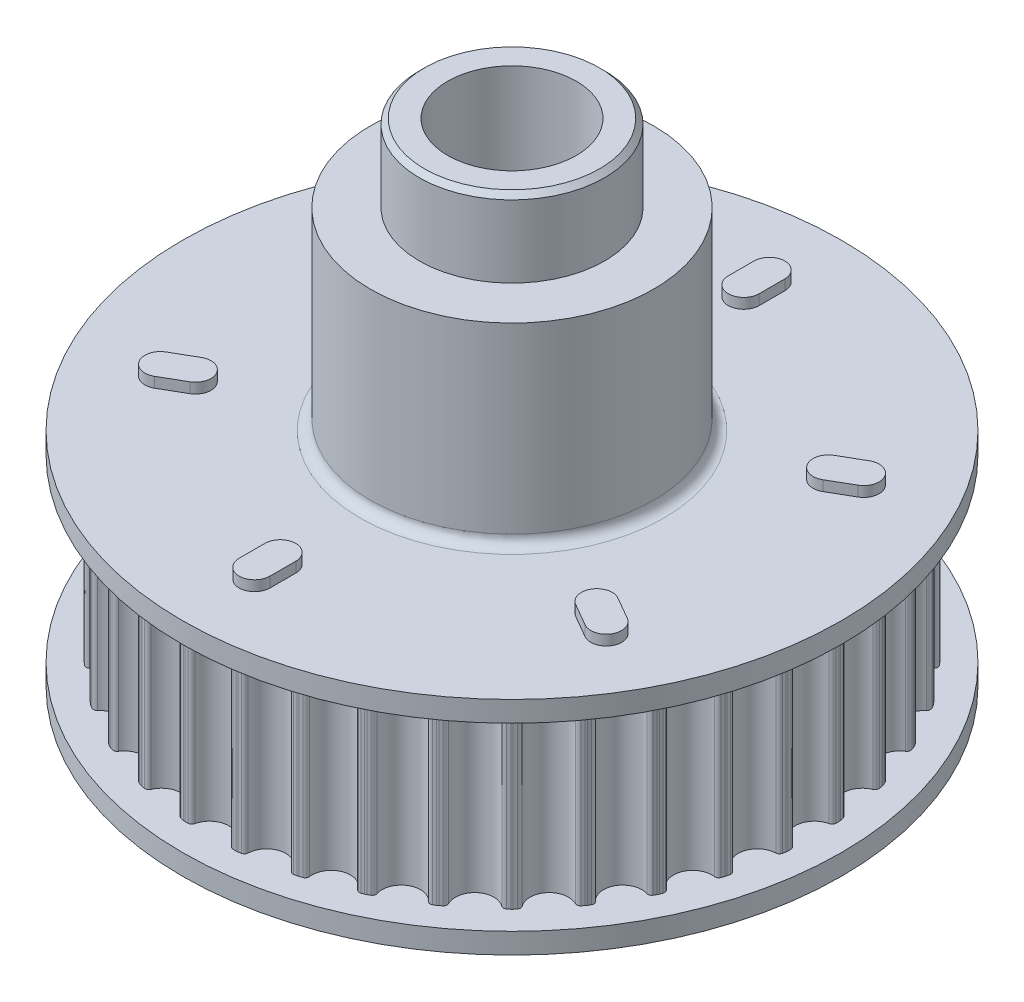
SolidWorks part; units mm, degrees
material "ABS"
ref_plane "Front Plane" through (0, 0, 0) normal (0, 0, 1) x (1, 0, 0)
ref_plane "Top Plane" through (0, 0, 0) normal (0, 1, 0) x (1, 0, 0)
ref_plane "Right Plane" through (0, 0, 0) normal (1, 0, 0) x (0, 0, -1)
sketch "Sketch1" plane through (0, 0, 0) normal (0, 1, 0) x (1, 0, 0)
  circle A0 centre (0, 0) radius 11.75
  circle A1 centre (0, 0) radius 2.5
  dimension "D1" = 23.5
  dimension "D2" = 5
extrude "Boss-Extrude1" add sketch "Sketch1" along normal blind 7
sketch "Sketch2" plane through (0, 7, 0) normal (0, 1, 0) x (1, 0, 0)
  line L0 (0, 0) -> (0, 11.75) construction
  line L1 (-0.8793, 11.708) -> (-1, 11.708)
  line L2 (0.8793, 11.708) -> (1, 11.708)
  line L3 (-1, 11.708) -> (-1, 11.9045)
  line L4 (-1, 11.9045) -> (1, 11.9045)
  line L5 (1, 11.9045) -> (1, 11.708)
  arc A0 (-0.7327, 11.59) -> (0.7327, 11.59) centre (0, 11.75) ccw
  arc A1 (-0.7327, 11.59) -> (-0.8793, 11.708) centre (-0.8793, 11.558) ccw
  arc A2 (0.7327, 11.59) -> (0.8793, 11.708) centre (0.8793, 11.558) cw
  dimension "D1" = 0.75
  dimension "D2" = 0.16
  dimension "D4" = 11.75
  dimension "D6" = 0
  dimension "D7" = 1
  dimension "D5" = 0.15
extrude "Cut-Extrude1" cut sketch "Sketch2" against normal through all
pattern_circular "CirPattern1" count 36 over 360 about axis through (0, 7, 0) along (0, 1, 0) of "Cut-Extrude1"
sketch "Sketch4" plane through (0, 0, 0) normal (0, -1, 0) x (1, 0, 0)
  circle A0 centre (0, 0) radius 3.15
  circle A1 centre (0, 0) radius 12.8
  dimension "D1" = 25.6
extrude "Boss-Extrude4" add sketch "Sketch4" along normal blind 0.8
sketch "Sketch5" plane through (0, 7, 0) normal (0, 1, 0) x (1, 0, 0)
  circle A0 centre (0, 0) radius 2.5
  circle A1 centre (0, 0) radius 12.8
  dimension "D1" = 25.6
  dimension "D2" = 5
extrude "Boss-Extrude5" add sketch "Sketch5" along normal blind 0.8
sketch "Sketch6" plane through (0, 7.8, 0) normal (0, 1, 0) x (1, 0, 0)
  circle A0 centre (0, 0) radius 2.5
  circle A1 centre (0, 0) radius 5.5
  dimension "D1" = 11
  dimension "D2" = 5
extrude "Boss-Extrude6" add sketch "Sketch6" along normal blind 7.5
fillet "Fillet4" radius 0.4 1 edges at (0, 7.8, 5.5)
sketch "Sketch14" plane through (0, -0.8, 0) normal (0, -1, 0) x (1, 0, 0)
  circle A0 centre (0, 0) radius 4.25
  dimension "D1" = 8.5
extrude "Cut-Extrude5" cut sketch "Sketch14" against normal blind 3
sketch "Sketch16" plane through (0, 15.3, 0) normal (0, 1, 0) x (1, 0, 0)
  circle A0 centre (0, 0) radius 3.6
  circle A1 centre (0, 0) radius 2.5
  dimension "D1" = 7.2
  dimension "D2" = 5
extrude "Boss-Extrude7" add sketch "Sketch16" along normal blind 3
sketch "Sketch17" plane through (0, 2.2, 0) normal (0, -1, 0) x (1, 0, 0)
  circle A0 centre (0, 0) radius 3.6
  dimension "D1" = 7.2
extrude "Cut-Extrude6" cut sketch "Sketch17" against normal blind 1
chamfer "Chamfer1" distance 0.2 angle 45 1 edges at (0, 18.3, 3.6)
sketch "Sketch18" plane through (0, 7.8, 0) normal (0, 1, 0) x (1, 0, 0)
  line L0 (0, 9) -> (0, 10) construction
  line L1 (-0.6, 9) -> (-0.6, 10)
  line L2 (0.6, 9) -> (0.6, 10)
  line L3 (7.7942, 4.5) -> (8.6603, 5) construction
  line L4 (7.4942, 5.0196) -> (8.3603, 5.5196)
  line L5 (8.0942, 3.9804) -> (8.9603, 4.4804)
  line L6 (7.7942, -4.5) -> (8.6603, -5) construction
  line L7 (8.0942, -3.9804) -> (8.9603, -4.4804)
  line L8 (7.4942, -5.0196) -> (8.3603, -5.5196)
  line L9 (0, -9) -> (0, -10) construction
  line L10 (0.6, -9) -> (0.6, -10)
  line L11 (-0.6, -9) -> (-0.6, -10)
  line L12 (-7.7942, -4.5) -> (-8.6603, -5) construction
  line L13 (-7.4942, -5.0196) -> (-8.3603, -5.5196)
  line L14 (-8.0942, -3.9804) -> (-8.9603, -4.4804)
  line L15 (-7.7942, 4.5) -> (-8.6603, 5) construction
  line L16 (-8.0942, 3.9804) -> (-8.9603, 4.4804)
  line L17 (-7.4942, 5.0196) -> (-8.3603, 5.5196)
  arc A0 (-0.6, 9) -> (0.6, 9) centre (0, 9) ccw
  arc A1 (0.6, 10) -> (-0.6, 10) centre (0, 10) ccw
  arc A2 (7.4942, 5.0196) -> (8.0942, 3.9804) centre (7.7942, 4.5) ccw
  arc A3 (8.9603, 4.4804) -> (8.3603, 5.5196) centre (8.6603, 5) ccw
  arc A4 (8.0942, -3.9804) -> (7.4942, -5.0196) centre (7.7942, -4.5) ccw
  arc A5 (8.3603, -5.5196) -> (8.9603, -4.4804) centre (8.6603, -5) ccw
  arc A6 (0.6, -9) -> (-0.6, -9) centre (0, -9) ccw
  arc A7 (-0.6, -10) -> (0.6, -10) centre (0, -10) ccw
  arc A8 (-7.4942, -5.0196) -> (-8.0942, -3.9804) centre (-7.7942, -4.5) ccw
  arc A9 (-8.9603, -4.4804) -> (-8.3603, -5.5196) centre (-8.6603, -5) ccw
  arc A10 (-8.0942, 3.9804) -> (-7.4942, 5.0196) centre (-7.7942, 4.5) ccw
  arc A11 (-8.3603, 5.5196) -> (-8.9603, 4.4804) centre (-8.6603, 5) ccw
  point P3 (0, 9.5)
  point P13 (8.2272, 4.75)
  point P20 (8.2272, -4.75)
  point P27 (0, -9.5)
  point P34 (-8.2272, -4.75)
  point P41 (-8.2272, 4.75)
  point P46 (0, 0)
  dimension "D1" = 0.6
  dimension "D2" = 1
  dimension "D3" = 9
  dimension "D4" = 6
extrude "Boss-Extrude8" add sketch "Sketch18" along normal blind 0.4
chamfer "Chamfer2" distance 1 angle 45 1 edges at (0, 3.2, -3.6)
